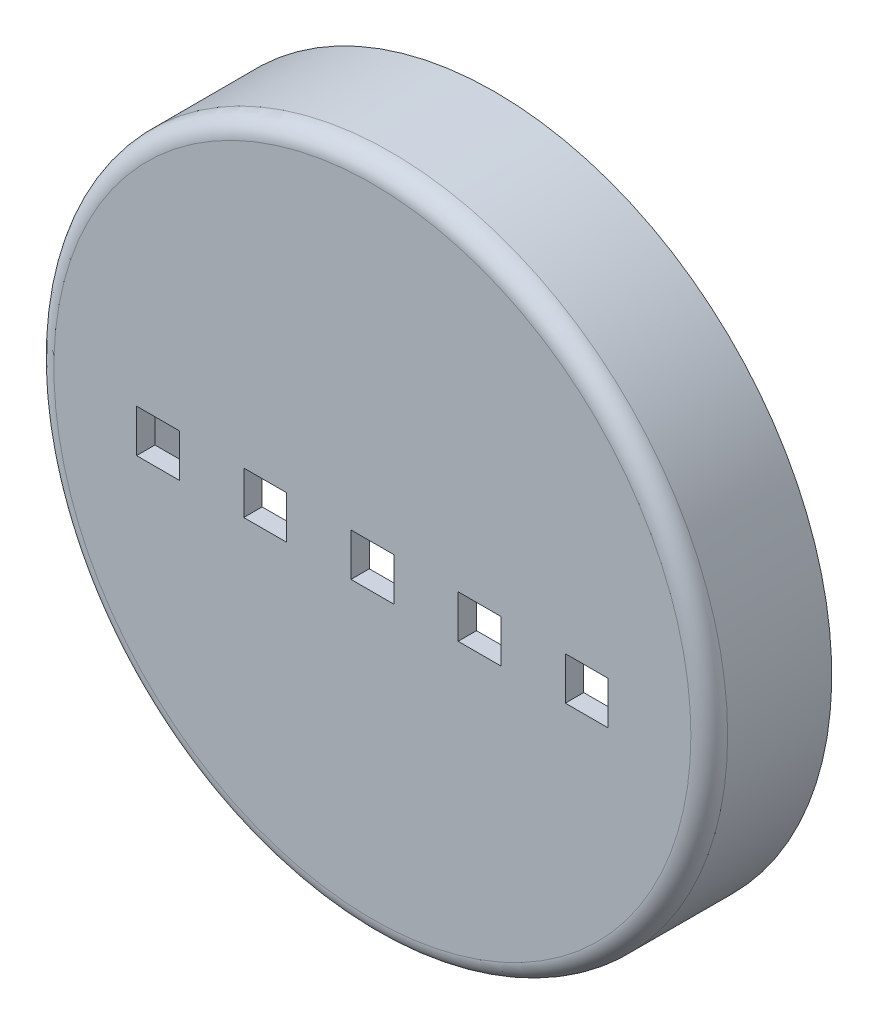
SolidWorks part; units mm, degrees
ref_plane "Front Plane" through (0, 0, 0) normal (0, 0, 1) x (1, 0, 0)
ref_plane "Top Plane" through (0, 0, 0) normal (0, 1, 0) x (1, 0, 0)
ref_plane "Right Plane" through (0, 0, 0) normal (1, 0, 0) x (0, 0, -1)
sketch "Sketch1" plane through (0, 0, 0) normal (0, 0, 1) x (1, 0, 0)
  circle A0 centre (328.3894, 629.2716) radius 55
  circle A1 centre (328.3894, 629.2716) radius 51
  dimension "D1" = 110
  dimension "D2" = 102
extrude "Boss-Extrude2" add sketch "Sketch1" along normal blind 20 contours A0
sketch "Sketch2" plane through (0, 0, 0) normal (0, 0, -1) x (-1, 0, 0)
  circle A0 centre (-328.6286, 629.3843) radius 51
  dimension "D1" = 102
extrude "Cut-Extrude1" cut sketch "Sketch2" against normal blind 17
sketch "Sketch10" plane through (0, 0, 17) normal (0, 0, -1) x (-1, 0, 0)
  line L0 (-328.3894, 627.0764) -> (-374.3894, 627.0764)
  line L1 (-378.3894, 627.0764) -> (-278.3894, 627.0764)
  line L2 (-378.3894, 627.0764) -> (-378.3894, 647.0764)
  line L3 (-378.3894, 647.0764) -> (-278.3894, 647.0764)
  line L4 (-278.3894, 627.0764) -> (-278.3894, 647.0764)
  line L6 (-331.8894, 630.5764) -> (-324.8894, 630.5764)
  line L7 (-331.8894, 630.5764) -> (-331.8894, 623.5764)
  line L8 (-331.8894, 623.5764) -> (-324.8894, 623.5764)
  line L9 (-324.8894, 630.5764) -> (-324.8894, 623.5764)
  line L10 (-314.3894, 630.5764) -> (-307.3894, 630.5764)
  line L11 (-314.3894, 630.5764) -> (-314.3894, 623.5764)
  line L12 (-314.3894, 623.5764) -> (-307.3894, 623.5764)
  line L13 (-307.3894, 630.5764) -> (-307.3894, 623.5764)
  line L14 (-296.8894, 630.5764) -> (-289.8894, 630.5764)
  line L15 (-296.8894, 630.5764) -> (-296.8894, 623.5764)
  line L16 (-296.8894, 623.5764) -> (-289.8894, 623.5764)
  line L17 (-289.8894, 630.5764) -> (-289.8894, 623.5764)
  line L18 (-349.3894, 630.5764) -> (-342.3894, 630.5764)
  line L19 (-349.3894, 630.5764) -> (-349.3894, 623.5764)
  line L20 (-349.3894, 623.5764) -> (-342.3894, 623.5764)
  line L21 (-342.3894, 630.5764) -> (-342.3894, 623.5764)
  line L22 (-366.8894, 630.5764) -> (-359.8894, 630.5764)
  line L23 (-366.8894, 630.5764) -> (-366.8894, 623.5764)
  line L24 (-366.8894, 623.5764) -> (-359.8894, 623.5764)
  line L25 (-359.8894, 630.5764) -> (-359.8894, 623.5764)
  circle A0 centre (-328.3894, 629.2716) radius 55 construction
  circle A1 centre (-374.3894, 627.0764) radius 1.5
  circle A2 centre (-282.3894, 627.0764) radius 1.5
  dimension "D5" = 3
  dimension "D7" = 3
  dimension "D1" = 100
  dimension "D2" = 50
  dimension "D3" = 20
  dimension "D4" = 2.1952
  dimension "D6" = 4
  dimension "D8" = 4
  dimension "D9" = 7
  dimension "D10" = 7
  dimension "D11" = 3.5
  dimension "D12" = 7
  dimension "D13" = 7
  dimension "D14" = 7
  dimension "D15" = 7
  dimension "D16" = 3.5
  dimension "D17" = 3.5
  dimension "D18" = 7
  dimension "D19" = 7
  dimension "D20" = 3.5
  dimension "D21" = 3.5
  dimension "D22" = 7
  dimension "D23" = 7
  dimension "D24" = 3.5
  dimension "D25" = 17.5
  dimension "D26" = 17.5
  dimension "D27" = 17.5
  dimension "D28" = 17.5
extrude "Boss-Extrude3" add sketch "Sketch10" along normal blind 10 contours A1 | A2
extrude "Cut-Extrude4" cut sketch "Sketch10<3>" against normal blind 10 contours L25 L22 L23 L1 | L25 L1 L23 L24 | L21 L18 L19 L0 | L21 L0 L19 L20 | L9 L6 L7 L0 L1 | L9 L1 L0 L7 L8 | L13 L10 L11 L1 | L17 L14 L15 L1 | L17 L1 L15 L16 | L12 L13 L10 L11 region at (363.3894, 628.8264, 17) region at (363.3894, 625.3264, 17) region at (345.8894, 628.8264, 17) region at (345.8894, 625.3264, 17) region at (328.3894, 628.8264, 17) region at (328.3894, 625.3264, 17) region at (310.8894, 628.8264, 17) region at (293.3894, 625.3264, 17) region at (293.3894, 628.8264, 17)
sketch "Sketch10<3>" plane through (0, 0, 17) normal (0, 0, -1) x (-1, 0, 0) same geometry as "Sketch10"
fillet "Fillet1" radius 3 1 edges at (383.3894, 629.2716, 20)
sketch "Sketch11" plane through (0, 0, 17) normal (0, 0, -1) x (-1, 0, 0)
  line L1 (-352.6286, 667.3843) -> (-304.6286, 667.3843)
  line L2 (-352.6286, 667.3843) -> (-352.6286, 591.3843)
  line L3 (-352.6286, 591.3843) -> (-304.6286, 591.3843)
  line L4 (-304.6286, 667.3843) -> (-304.6286, 591.3843)
  circle A2 centre (-306.6286, 665.3843) radius 4
  circle A3 centre (-350.6286, 665.3843) radius 4
  circle A4 centre (-328.6286, 629.3843) radius 51 construction
  circle A5 centre (-350.6286, 593.3843) radius 4
  circle A6 centre (-306.6286, 593.3843) radius 4
  point P14 (0, 0)
  point P15 (0, 0)
  dimension "D3" = 2
  dimension "D7" = 2
  dimension "D9" = 8
  dimension "D11" = 8
  dimension "D14" = 38
  dimension "D5" = 8
  dimension "D16" = 8
  dimension "D1" = 76
  dimension "D2" = 48
  dimension "D4" = 2
  dimension "D6" = 2
  dimension "D8" = 2
  dimension "D10" = 2
  dimension "D12" = 2
  dimension "D13" = 2
  dimension "D15" = 24
extrude "Boss-Extrude4" add sketch "Sketch11" along normal blind 20 contours A3 | A2 | A6 | A5
hole_wizard "Tap Drill for #4-40 Tap1" positions "Sketch12" profile "Sketch13" hole size "#4-40" standard "ANSI Inch"
sketch "Sketch12" plane through (0, 0, -3) normal (0, 0, -1) x (-1, 0, 0)
  point P0 (-350.6286, 665.3843)
  point P3 (-306.6286, 665.3843)
  point P6 (-350.6286, 593.3843)
  point P9 (-306.6286, 593.3843)
sketch "Sketch13" plane through (350.6286, 665.3843, -3) normal (1, 0, 0) x (0, 1, 0)
  line L0 (0, 0) -> (0, 13.7292)
  line L1 (0, 13.7292) -> (1.1303, 13.05)
  line L2 (1.1303, 13.05) -> (1.1303, 0)
  line L5 (1.1303, 0) -> (0, 0)
  line L10 (0, 13.7292) -> (-1.1303, 13.05) construction
  line L11 (0, -6.35) -> (0, 107.95) construction
  dimension "Hole Dia." = 2.2606
  dimension "Hole Depth" = 13.05
  dimension "Drill Angle" = 118
sketch "Sketch14" plane through (0, 623.5764, 0) normal (0, 1, 0) x (1, 0, 0)
  line L0 (383.3894, 0) -> (273.3894, 0) construction
  circle A0 centre (330.3796, 0) radius 2.5
  dimension "D1" = 5
  dimension "D2" = 0
extrude "Cut-Extrude5" cut sketch "Sketch14" against normal blind 50
